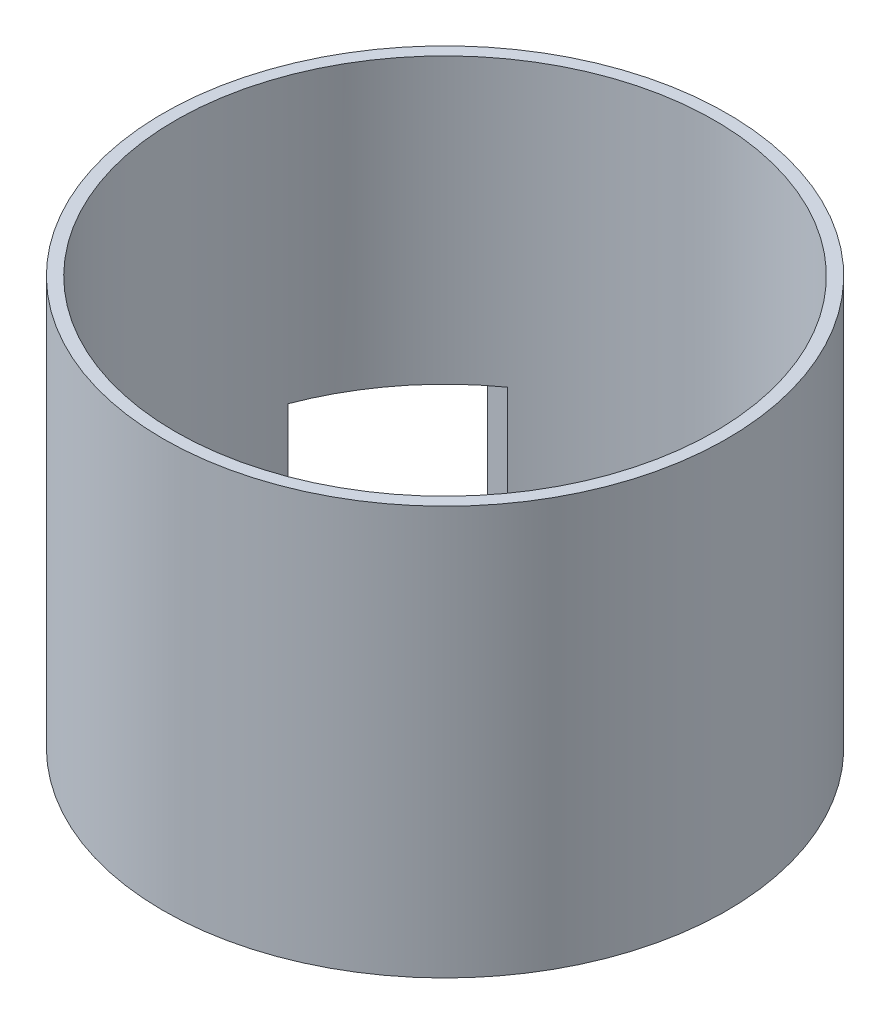
SolidWorks part; units mm, degrees
ref_plane "Front Plane" through (0, 0, 0) normal (0, 0, 1) x (1, 0, 0)
ref_plane "Top Plane" through (0, 0, 0) normal (0, 1, 0) x (1, 0, 0)
ref_plane "Right Plane" through (0, 0, 0) normal (1, 0, 0) x (0, 0, -1)
sketch "Sketch1" plane through (0, 0, 0) normal (0, 1, 0) x (1, 0, 0)
  circle A0 centre (0, 0) radius 69
  circle A1 centre (0, 0) radius 66
  dimension "D1" = 138
  dimension "D2" = 3
extrude "Boss-Extrude1" add sketch "Sketch1" along normal blind 100
sketch "Sketch2" plane through (0, 0, 0) normal (0, 1, 0) x (1, 0, 0)
  line L0 (0, 0) -> (-101.9987, 0) construction
  line L1 (0, 0) -> (-90.6575, -52.3411) construction
  line L2 (-64.9519, -37.5) -> (-82.6631, -6.8233) construction
  dimension "D1" = 30
  dimension "D2" = 75
ref_plane "Plane1" through (-64.9519, 0, 37.5) normal (0.866, 0, -0.5) x (-0.5, 0, -0.866)
sketch "Sketch3" plane through (-64.9519, 0, 37.5) normal (0.866, 0, -0.5) x (-0.5, 0, -0.866)
  line L0 (10, 31.5) -> (10, 59.5)
  line L1 (10, 59.5) -> (-10, 59.5)
  line L2 (-10, 59.5) -> (-10, 31.5)
  line L3 (-10, 31.5) -> (10, 31.5)
  point P2 (0, 31.5)
  dimension "D1" = 20
  dimension "D2" = 31.5
  dimension "D3" = 28
  dimension "D4" = 0
extrude "Cut-Extrude1" cut sketch "Sketch3" along normal up to next
fillet "Fillet1" radius 3 4 edges at (-52.8113, 31.5, 42.0376) (-62.8113, 31.5, 24.7171) (-52.8113, 59.5, 42.0376) (-62.8113, 59.5, 24.7171)
sketch "Sketch4" plane through (0, 0, 0) normal (1, 0, 0) x (0, 0, -1)
  line L1 (23.3, 0) -> (53.7, 0)
  line L2 (23.3, 0) -> (23.3, 30.4)
  line L3 (23.3, 30.4) -> (53.7, 30.4)
  line L4 (53.7, 0) -> (53.7, 30.4)
  dimension "D1" = 30.4
  dimension "D2" = 30.4
  dimension "D3" = 0
  dimension "D4" = 23.3
extrude "Cut-Extrude2" cut sketch "Sketch4" against normal through all
